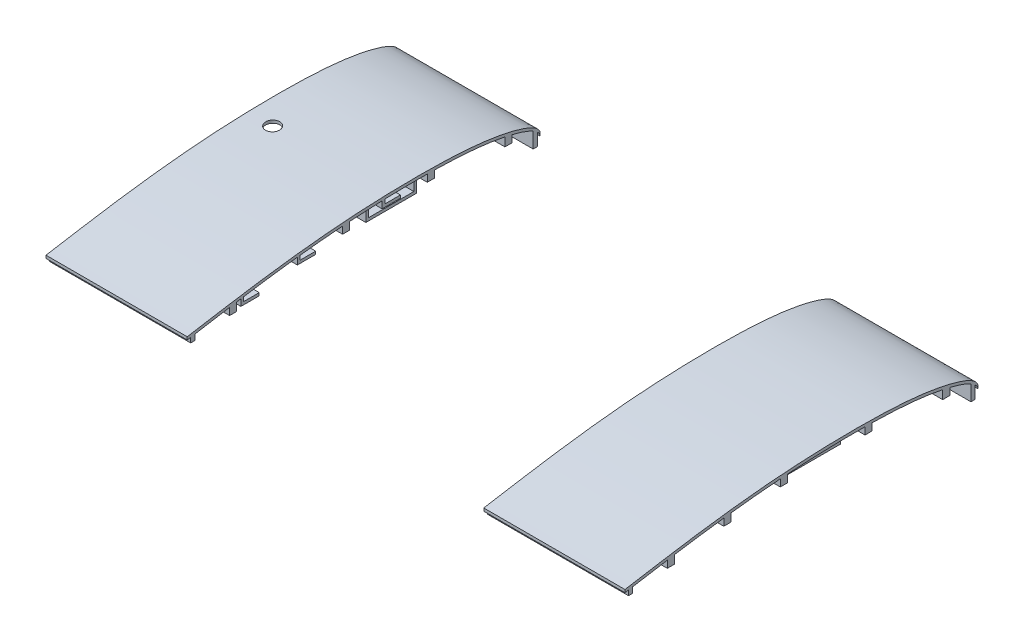
SolidWorks part; units mm, degrees
material "Nylon 12"
ref_plane "Piano frontale" through (0, 0, 0) normal (0, 0, 1) x (1, 0, 0)
ref_plane "Piano superiore" through (0, 0, 0) normal (0, 1, 0) x (1, 0, 0)
ref_plane "Piano destro" through (0, 0, 0) normal (1, 0, 0) x (0, 0, -1)
curve "CurvaProfiloAltoSinistro"
  spline degree 3 poles (-210, 41.3424, 123.285) (-210, 41.117, 125.4273) (-210, 41.4162, 123.3284) (-210, 41.7229, 121.6445) (-210, 42.4159, 117.6221) (-210, 43.2689, 112.7464) (-210, 44.3518, 106.3634) (-210, 45.4633, 98.9772) (-210, 46.9012, 90.5604) (-210, 48.3015, 81.3004) (-210, 49.8024, 71.1631) (-210, 51.2862, 60.3524) (-210, 52.7193, 48.9891) (-210, 54.0516, 37.1914) (-210, 55.2293, 25.0724) (-210, 56.2223, 12.7438) (-210, 56.9956, 0.3116) (-210, 57.5534, -12.1112) (-210, 57.8967, -24.403) (-210, 58.0348, -36.4331) (-210, 57.962, -48.0686) (-210, 57.6641, -59.1835) (-210, 57.1309, -69.6671) (-210, 56.3294, -79.427) (-210, 55.2678, -88.3926) (-210, 53.9584, -96.5028) (-210, 52.4539, -103.7012) (-210, 50.8113, -109.9251) (-210, 49.0836, -115.1191) (-210, 47.2882, -119.2301) (-210, 45.4084, -122.2711) (-210, 43.4757, -124.1874) (-210, 41.9627, -124.9688) (-210, 40.7595, -125.0213) (-210, 39.4585, -124.5051) (-210, 38.3042, -122.3747) (-210, 37.1296, -119.3023) (-210, 36.2413, -114.9281) (-210, 35.5726, -109.3738) (-210, 35.1578, -102.5878) (-210, 34.905, -94.6381) (-210, 34.7886, -85.6028) (-210, 34.8146, -75.6013) (-210, 34.9515, -64.7547) (-210, 35.2224, -53.1982) (-210, 35.6332, -41.0592) (-210, 36.2314, -28.4539) (-210, 37.0173, -15.4799) (-210, 37.9504, -2.2329) (-210, 38.9791, 11.1764) (-210, 40.022, 24.6158) (-210, 41.0098, 37.9314) (-210, 41.876, 50.9537) (-210, 42.5596, 63.4999) (-210, 43.0032, 75.3712) (-210, 43.1376, 86.3376) (-210, 42.9932, 96.1842) (-210, 42.6673, 104.6804) (-210, 42.2441, 111.8065) (-210, 41.8557, 117.1894) (-210, 41.4787, 121.5181) (-210, 41.3424, 123.285) (-210, 41.117, 125.4273) (-210, 41.4162, 123.3284) knots -0.014202 -0.006329 -0.001589 0 0.001576 0.006211 0.01368 0.023764 0.036307 0.051658 0.068045 0.086769 0.107053 0.128647 0.151303 0.174786 0.19886 0.223309 0.247929 0.272522 0.296848 0.320648 0.343669 0.365658 0.3864 0.405741 0.423561 0.439779 0.454311 0.467034 0.477831 0.486643 0.493542 0.498786 0.50271 0.50309 0.505896 0.510322 0.516831 0.525521 0.536535 0.549945 0.565696 0.583577 0.603379 0.624844 0.647727 0.671743 0.696673 0.722357 0.748609 0.77521 0.801891 0.828329 0.854175 0.879074 0.902636 0.924421 0.943939 0.960827 0.974827 0.985798 0.993671 0.998411 1 1.001576 1.006211 1.01368 periodic
curve "CurvaProfiloBassoSinistro"
  spline degree 3 poles (-210, 43.3424, 123.285) (-210, 43.117, 125.4273) (-210, 43.4162, 123.3284) (-210, 43.7229, 121.6445) (-210, 44.4159, 117.6221) (-210, 45.2689, 112.7464) (-210, 46.3518, 106.3634) (-210, 47.4633, 98.9772) (-210, 48.9012, 90.5604) (-210, 50.3015, 81.3004) (-210, 51.8024, 71.1631) (-210, 53.2862, 60.3524) (-210, 54.7193, 48.9891) (-210, 56.0516, 37.1914) (-210, 57.2293, 25.0724) (-210, 58.2223, 12.7438) (-210, 58.9956, 0.3116) (-210, 59.5534, -12.1112) (-210, 59.8967, -24.403) (-210, 60.0348, -36.4331) (-210, 59.962, -48.0686) (-210, 59.6641, -59.1835) (-210, 59.1309, -69.6671) (-210, 58.3294, -79.427) (-210, 57.2678, -88.3926) (-210, 55.9584, -96.5028) (-210, 54.4539, -103.7012) (-210, 52.8113, -109.9251) (-210, 51.0836, -115.1191) (-210, 49.2882, -119.2301) (-210, 47.4084, -122.2711) (-210, 45.4757, -124.1874) (-210, 43.9627, -124.9688) (-210, 42.7595, -125.0213) (-210, 41.4585, -124.5051) (-210, 40.3042, -122.3747) (-210, 39.1296, -119.3023) (-210, 38.2413, -114.9281) (-210, 37.5726, -109.3738) (-210, 37.1578, -102.5878) (-210, 36.905, -94.6381) (-210, 36.7886, -85.6028) (-210, 36.8146, -75.6013) (-210, 36.9515, -64.7547) (-210, 37.2224, -53.1982) (-210, 37.6332, -41.0592) (-210, 38.2314, -28.4539) (-210, 39.0173, -15.4799) (-210, 39.9504, -2.2329) (-210, 40.9791, 11.1764) (-210, 42.022, 24.6158) (-210, 43.0098, 37.9314) (-210, 43.876, 50.9537) (-210, 44.5596, 63.4999) (-210, 45.0032, 75.3712) (-210, 45.1376, 86.3376) (-210, 44.9932, 96.1842) (-210, 44.6673, 104.6804) (-210, 44.2441, 111.8065) (-210, 43.8557, 117.1894) (-210, 43.4787, 121.5181) (-210, 43.3424, 123.285) (-210, 43.117, 125.4273) (-210, 43.4162, 123.3284) knots -0.014202 -0.006329 -0.001589 0 0.001576 0.006211 0.01368 0.023764 0.036307 0.051658 0.068045 0.086769 0.107053 0.128647 0.151303 0.174786 0.19886 0.223309 0.247929 0.272522 0.296848 0.320648 0.343669 0.365658 0.3864 0.405741 0.423561 0.439779 0.454311 0.467034 0.477831 0.486643 0.493542 0.498786 0.50271 0.50309 0.505896 0.510322 0.516831 0.525521 0.536535 0.549945 0.565696 0.583577 0.603379 0.624844 0.647727 0.671743 0.696673 0.722357 0.748609 0.77521 0.801891 0.828329 0.854175 0.879074 0.902636 0.924421 0.943939 0.960827 0.974827 0.985798 0.993671 0.998411 1 1.001576 1.006211 1.01368 periodic
ref_plane "PianoProfiloSinistro" through (-210, 0, 0) normal (1, 0, 0) x (0, 0, -1)
sketch "ProfiloSinistro" plane through (-210, 0, 0) normal (1, 0, 0) x (0, 0, -1)
  line L0 (-125, 43.17) -> (-125, 41.17)
  line L1 (125.0001, 43.1872) -> (125.0001, 41.1872)
  line L2 (122.5001, 43.1872) -> (127.5001, 43.1872) construction
  line L4 (-50, 52.5724) -> (-50, 46.9555)
  line L5 (-50, 46.9555) -> (-55, 46.9555)
  line L6 (-55, 51.9555) -> (-55, 46.9555)
  line L8 (-90, 46.9622) -> (-90, 41.143)
  line L9 (-90, 41.143) -> (-95, 41.143)
  line L10 (-95, 46.143) -> (-95, 41.143)
  line L12 (-10, 56.3746) -> (-10, 51.0196)
  line L13 (-10, 51.0196) -> (-15, 51.0196)
  line L14 (-15, 56.0196) -> (-15, 51.0196)
  line L16 (50.0001, 57.8877) -> (50.0001, 52.8877)
  line L17 (50.0001, 52.8877) -> (45.0001, 52.8877)
  line L18 (45.0001, 57.965) -> (45.0001, 52.8877)
  line L20 (105.0001, 52.079) -> (105.0001, 47.079)
  line L21 (105.0001, 47.079) -> (100.0001, 47.079)
  line L22 (100.0001, 53.212) -> (100.0001, 47.079)
  line L24 (137.7468, 0) -> (-137.7468, 0) construction
  spline S0 degree 3 poles (-123.3284, 43.4162) (-125.4273, 43.117) (-123.285, 43.3424) (-121.5181, 43.4787) (-117.1894, 43.8557) (-111.8065, 44.2441) (-104.6804, 44.6673) (-96.1842, 44.9932) (-86.3376, 45.1376) (-75.3712, 45.0032) (-63.4999, 44.5596) (-50.9537, 43.876) (-37.9314, 43.0098) (-24.6158, 42.022) (-11.1764, 40.9791) (2.2329, 39.9504) (15.4799, 39.0173) (28.4539, 38.2314) (41.0592, 37.6332) (53.1982, 37.2224) (64.7547, 36.9515) (75.6013, 36.8146) (85.6028, 36.7886) (94.6381, 36.905) (102.5878, 37.1578) (109.3738, 37.5726) (114.9281, 38.2413) (119.3023, 39.1296) (122.3747, 40.3042) (124.5051, 41.4585) (125.0213, 42.7595) (124.9688, 43.9627) (124.1874, 45.4757) (122.2711, 47.4084) (119.2301, 49.2882) (115.1191, 51.0836) (109.9251, 52.8113) (103.7012, 54.4539) (96.5028, 55.9584) (88.3926, 57.2678) (79.427, 58.3294) (69.6671, 59.1309) (59.1835, 59.6641) (48.0686, 59.962) (36.4331, 60.0348) (24.403, 59.8967) (12.1112, 59.5534) (-0.3116, 58.9956) (-12.7438, 58.2223) (-25.0724, 57.2293) (-37.1914, 56.0516) (-48.9891, 54.7193) (-60.3524, 53.2862) (-71.1631, 51.8024) (-81.3004, 50.3015) (-90.5604, 48.9012) (-98.9772, 47.4633) (-106.3634, 46.3518) (-112.7464, 45.2689) (-117.6221, 44.4159) (-121.6445, 43.7229) (-123.3284, 43.4162) (-125.4273, 43.117) (-123.285, 43.3424) knots -0.01368 -0.006211 -0.001576 0 0.001589 0.006329 0.014202 0.025173 0.039173 0.056061 0.075579 0.097364 0.120926 0.145825 0.171671 0.198109 0.22479 0.251391 0.277643 0.303327 0.328257 0.352273 0.375156 0.396621 0.416423 0.434304 0.450055 0.463465 0.474479 0.483169 0.489678 0.494104 0.49691 0.49729 0.501214 0.506458 0.513357 0.522169 0.532966 0.545689 0.560221 0.576439 0.594259 0.6136 0.634342 0.656331 0.679352 0.703152 0.727478 0.752071 0.776691 0.80114 0.825214 0.848697 0.871353 0.892947 0.913231 0.931955 0.948342 0.963693 0.976236 0.98632 0.993789 0.998424 1 1.001589 1.006329 1.014202 only from (-125, 43.17) to (-125, 43.17) construction
  spline S1 degree 3 poles (125.0001, 43.1872) (125.0001, 43.2458) (124.9661, 43.968) (124.1874, 45.4757) (122.2711, 47.4084) (119.2301, 49.2882) (115.1191, 51.0836) (109.9251, 52.8113) (103.7012, 54.4539) (96.5028, 55.9584) (88.3926, 57.2678) (79.427, 58.3294) (69.6671, 59.1309) (59.1835, 59.6641) (48.0686, 59.962) (36.4331, 60.0348) (24.403, 59.8967) (12.1112, 59.5534) (-0.3116, 58.9956) (-12.7438, 58.2223) (-25.0724, 57.2293) (-37.1914, 56.0516) (-48.9891, 54.7193) (-60.3524, 53.2862) (-71.1631, 51.8024) (-81.3004, 50.3015) (-90.5604, 48.9012) (-98.9772, 47.4633) (-106.3634, 46.3518) (-112.7464, 45.2689) (-117.6221, 44.4159) (-121.6445, 43.7229) (-123.3284, 43.4162) (-124.9998, 43.178) (-125, 43.17) knots 0.496944 0.496944 0.496944 0.496944 0.49729 0.501214 0.506458 0.513357 0.522169 0.532966 0.545689 0.560221 0.576439 0.594259 0.6136 0.634342 0.656331 0.679352 0.703152 0.727478 0.752071 0.776691 0.80114 0.825214 0.848697 0.871353 0.892947 0.913231 0.931955 0.948342 0.963693 0.976236 0.98632 0.993789 0.998424 1 1 1 1
  spline S3 degree 3 poles (125.0001, 41.1872) (125.0001, 41.2458) (124.9661, 41.968) (124.1874, 43.4757) (122.2711, 45.4084) (119.2301, 47.2882) (115.1191, 49.0836) (110.2558, 50.7013) (106.751, 51.647) (105.0001, 52.079) knots 0.496944 0.496944 0.496944 0.496944 0.49729 0.501214 0.506458 0.513357 0.522169 0.532966 0.54363 0.54363 0.54363 0.54363
  spline S4 degree 3 poles (-95, 46.143) (-96.3836, 45.9134) (-100.3273, 45.2601) (-106.3634, 44.3518) (-112.7464, 43.2689) (-117.6221, 42.4159) (-121.6445, 41.7229) (-123.3284, 41.4162) (-124.9998, 41.178) (-125, 41.17) knots 0.940049 0.940049 0.940049 0.940049 0.948342 0.963693 0.976236 0.98632 0.993789 0.998424 1 1 1 1
  spline S5 degree 3 poles (-55, 51.9555) (-56.8432, 51.723) (-62.3071, 51.0179) (-71.1631, 49.8024) (-80.9841, 48.3484) (-87.1888, 47.411) (-90, 46.9622) knots 0.860366 0.860366 0.860366 0.860366 0.871353 0.892947 0.913231 0.930064 0.930064 0.930064 0.930064
  spline S6 degree 3 poles (-15, 56.0196) (-18.3794, 55.7673) (-25.8142, 55.1572) (-37.1914, 54.0516) (-45.4742, 53.1162) (-49.7084, 52.6076) (-50, 52.5724) knots 0.781099 0.781099 0.781099 0.781099 0.80114 0.825214 0.848697 0.850435 0.850435 0.850435 0.850435
  spline S7 degree 3 poles (45.0001, 57.965) (42.1885, 57.9961) (35.3522, 58.0224) (24.403, 57.8967) (12.1112, 57.5534) (0.613, 57.0371) (-6.7697, 56.5921) (-10, 56.3746) knots 0.662724 0.662724 0.662724 0.662724 0.679352 0.703152 0.727478 0.752071 0.771218 0.771218 0.771218 0.771218
  spline S8 degree 3 poles (100.0001, 53.212) (98.9265, 53.4351) (95.1591, 54.1753) (88.3926, 55.2678) (79.427, 56.3294) (69.6671, 57.1309) (59.7687, 57.6343) (53.1316, 57.8251) (50.0001, 57.8877) knots 0.553737 0.553737 0.553737 0.553737 0.560221 0.576439 0.594259 0.6136 0.634342 0.652866 0.652866 0.652866 0.652866
  point P24 (125.0001, 43.1872)
  dimension "D1" = 5
  dimension "D2" = 5
  dimension "D3" = 5.8192
  dimension "D4" = 41.17
  dimension "D5" = 46.143
  dimension "D6" = 30
  dimension "D7" = 41.143
  dimension "D8" = 5
  dimension "D9" = 43.1872
  dimension "D10" = 35
  dimension "D11" = 4.9933
  dimension "D12" = 46.9555
  dimension "D13" = 51.0196
  dimension "D14" = 35
  dimension "D15" = 56.0196
  dimension "D16" = 52.5724
  dimension "D17" = 56.3746
  dimension "D18" = 5.0773
  dimension "D19" = 5
  dimension "D20" = 55.0001
  dimension "D21" = 52.8877
  dimension "D22" = 47.079
  dimension "D23" = 50
  dimension "D24" = 6.133
  dimension "D25" = 5
  dimension "D26" = 20
  dimension "D27" = 2
extrude "ProfiloConRinforziSinistro" add sketch "ProfiloSinistro" along normal blind 105
ref_plane "PianoFrontale" through (0, 0, -125.0001) normal (0, 0, -1) x (-1, 0, 0)
sketch "Schizzo2" plane through (0, 0, -125.0001) normal (0, 0, -1) x (-1, 0, 0)
  line L0 (210, 34.6211) -> (210, -34.6211) construction
  line L1 (105, 43.1872) -> (210, 43.1872)
  line L2 (105, 43.1872) -> (105, -2.9128)
  line L3 (105, -2.9128) -> (210, -2.9128)
  line L4 (210, 43.1872) -> (210, -2.9128)
  line L6 (157.5, 43.1872) -> (157.5, -2.9128) construction
  circle A0 centre (174.165, 22.0872) radius 10
  dimension "D2" = 20
  dimension "D1" = 46.1
  dimension "D3" = 25
  dimension "D4" = 16.665
curve "CurvaProfiloAltoDestro"
  spline degree 3 poles (210, 43.3424, 123.285) (210, 43.117, 125.4273) (210, 43.4162, 123.3284) (210, 43.7229, 121.6445) (210, 44.4159, 117.6221) (210, 45.2689, 112.7464) (210, 46.3518, 106.3634) (210, 47.4633, 98.9772) (210, 48.9012, 90.5604) (210, 50.3015, 81.3004) (210, 51.8024, 71.1631) (210, 53.2862, 60.3524) (210, 54.7193, 48.9891) (210, 56.0516, 37.1914) (210, 57.2293, 25.0724) (210, 58.2223, 12.7438) (210, 58.9956, 0.3116) (210, 59.5534, -12.1112) (210, 59.8967, -24.403) (210, 60.0348, -36.4331) (210, 59.962, -48.0686) (210, 59.6641, -59.1835) (210, 59.1309, -69.6671) (210, 58.3294, -79.427) (210, 57.2678, -88.3926) (210, 55.9584, -96.5028) (210, 54.4539, -103.7012) (210, 52.8113, -109.9251) (210, 51.0836, -115.1191) (210, 49.2882, -119.2301) (210, 47.4084, -122.2711) (210, 45.4757, -124.1874) (210, 43.9627, -124.9688) (210, 42.7595, -125.0213) (210, 41.4585, -124.5051) (210, 40.3042, -122.3747) (210, 39.1296, -119.3023) (210, 38.2413, -114.9281) (210, 37.5726, -109.3738) (210, 37.1578, -102.5878) (210, 36.905, -94.6381) (210, 36.7886, -85.6028) (210, 36.8146, -75.6013) (210, 36.9515, -64.7547) (210, 37.2224, -53.1982) (210, 37.6332, -41.0592) (210, 38.2314, -28.4539) (210, 39.0173, -15.4799) (210, 39.9504, -2.2329) (210, 40.9791, 11.1764) (210, 42.022, 24.6158) (210, 43.0098, 37.9314) (210, 43.876, 50.9537) (210, 44.5596, 63.4999) (210, 45.0032, 75.3712) (210, 45.1376, 86.3376) (210, 44.9932, 96.1842) (210, 44.6673, 104.6804) (210, 44.2441, 111.8065) (210, 43.8557, 117.1894) (210, 43.4787, 121.5181) (210, 43.3424, 123.285) (210, 43.117, 125.4273) (210, 43.4162, 123.3284) knots -0.014202 -0.006329 -0.001589 0 0.001576 0.006211 0.01368 0.023764 0.036307 0.051658 0.068045 0.086769 0.107053 0.128647 0.151303 0.174786 0.19886 0.223309 0.247929 0.272522 0.296848 0.320648 0.343669 0.365658 0.3864 0.405741 0.423561 0.439779 0.454311 0.467034 0.477831 0.486643 0.493542 0.498786 0.50271 0.50309 0.505896 0.510322 0.516831 0.525521 0.536535 0.549945 0.565696 0.583577 0.603379 0.624844 0.647727 0.671743 0.696673 0.722357 0.748609 0.77521 0.801891 0.828329 0.854175 0.879074 0.902636 0.924421 0.943939 0.960827 0.974827 0.985798 0.993671 0.998411 1 1.001576 1.006211 1.01368 periodic
curve "CurvaProfiloBassoDestro"
  spline degree 3 poles (210, 41.3424, 123.285) (210, 41.117, 125.4273) (210, 41.4162, 123.3284) (210, 41.7229, 121.6445) (210, 42.4159, 117.6221) (210, 43.2689, 112.7464) (210, 44.3518, 106.3634) (210, 45.4633, 98.9772) (210, 46.9012, 90.5604) (210, 48.3015, 81.3004) (210, 49.8024, 71.1631) (210, 51.2862, 60.3524) (210, 52.7193, 48.9891) (210, 54.0516, 37.1914) (210, 55.2293, 25.0724) (210, 56.2223, 12.7438) (210, 56.9956, 0.3116) (210, 57.5534, -12.1112) (210, 57.8967, -24.403) (210, 58.0348, -36.4331) (210, 57.962, -48.0686) (210, 57.6641, -59.1835) (210, 57.1309, -69.6671) (210, 56.3294, -79.427) (210, 55.2678, -88.3926) (210, 53.9584, -96.5028) (210, 52.4539, -103.7012) (210, 50.8113, -109.9251) (210, 49.0836, -115.1191) (210, 47.2882, -119.2301) (210, 45.4084, -122.2711) (210, 43.4757, -124.1874) (210, 41.9627, -124.9688) (210, 40.7595, -125.0213) (210, 39.4585, -124.5051) (210, 38.3042, -122.3747) (210, 37.1296, -119.3023) (210, 36.2413, -114.9281) (210, 35.5726, -109.3738) (210, 35.1578, -102.5878) (210, 34.905, -94.6381) (210, 34.7886, -85.6028) (210, 34.8146, -75.6013) (210, 34.9515, -64.7547) (210, 35.2224, -53.1982) (210, 35.6332, -41.0592) (210, 36.2314, -28.4539) (210, 37.0173, -15.4799) (210, 37.9504, -2.2329) (210, 38.9791, 11.1764) (210, 40.022, 24.6158) (210, 41.0098, 37.9314) (210, 41.876, 50.9537) (210, 42.5596, 63.4999) (210, 43.0032, 75.3712) (210, 43.1376, 86.3376) (210, 42.9932, 96.1842) (210, 42.6673, 104.6804) (210, 42.2441, 111.8065) (210, 41.8557, 117.1894) (210, 41.4787, 121.5181) (210, 41.3424, 123.285) (210, 41.117, 125.4273) (210, 41.4162, 123.3284) knots -0.014202 -0.006329 -0.001589 0 0.001576 0.006211 0.01368 0.023764 0.036307 0.051658 0.068045 0.086769 0.107053 0.128647 0.151303 0.174786 0.19886 0.223309 0.247929 0.272522 0.296848 0.320648 0.343669 0.365658 0.3864 0.405741 0.423561 0.439779 0.454311 0.467034 0.477831 0.486643 0.493542 0.498786 0.50271 0.50309 0.505896 0.510322 0.516831 0.525521 0.536535 0.549945 0.565696 0.583577 0.603379 0.624844 0.647727 0.671743 0.696673 0.722357 0.748609 0.77521 0.801891 0.828329 0.854175 0.879074 0.902636 0.924421 0.943939 0.960827 0.974827 0.985798 0.993671 0.998411 1 1.001576 1.006211 1.01368 periodic
ref_plane "PianoProfiloDestro" through (210, 0, 0) normal (1, 0, 0) x (0, 0, -1)
sketch "Schizzo5" plane through (210, 0, 0) normal (1, 0, 0) x (0, 0, -1)
  line L0 (-125, 43.17) -> (-125, 41.17)
  line L1 (125.0001, 43.1872) -> (125.0001, 41.1872)
  line L2 (119.6216, 43.1872) -> (129.6216, 43.1872) construction
  line L3 (137.5117, 0) -> (-137.5117, 0) construction
  line L6 (-90, 46.9622) -> (-90, 41.143)
  line L7 (-90, 41.143) -> (-95, 41.143)
  line L8 (-95, 46.143) -> (-95, 41.143)
  line L10 (-50, 52.5724) -> (-50, 46.9555)
  line L11 (-50, 46.9555) -> (-55, 46.9555)
  line L12 (-55, 51.9555) -> (-55, 46.9555)
  line L14 (-10, 56.3746) -> (-10, 51.0196)
  line L15 (-10, 51.0196) -> (-15, 51.0196)
  line L16 (-15, 56.0196) -> (-15, 51.0196)
  line L18 (50.0001, 57.8877) -> (50.0001, 52.8877)
  line L19 (50.0001, 52.8877) -> (45.0001, 52.8877)
  line L20 (45.0001, 57.965) -> (45.0001, 52.8877)
  line L22 (105.0001, 52.079) -> (105.0001, 47.079)
  line L23 (105.0001, 47.079) -> (100.0001, 47.079)
  line L24 (100.0001, 53.212) -> (100.0001, 47.079)
  spline S0 degree 3 poles (-123.3284, 43.4162) (-125.4273, 43.117) (-123.285, 43.3424) (-121.5181, 43.4787) (-117.1894, 43.8557) (-111.8065, 44.2441) (-104.6804, 44.6673) (-96.1842, 44.9932) (-86.3376, 45.1376) (-75.3712, 45.0032) (-63.4999, 44.5596) (-50.9537, 43.876) (-37.9314, 43.0098) (-24.6158, 42.022) (-11.1764, 40.9791) (2.2329, 39.9504) (15.4799, 39.0173) (28.4539, 38.2314) (41.0592, 37.6332) (53.1982, 37.2224) (64.7547, 36.9515) (75.6013, 36.8146) (85.6028, 36.7886) (94.6381, 36.905) (102.5878, 37.1578) (109.3738, 37.5726) (114.9281, 38.2413) (119.3023, 39.1296) (122.3747, 40.3042) (124.5051, 41.4585) (125.0213, 42.7595) (124.9688, 43.9627) (124.1874, 45.4757) (122.2711, 47.4084) (119.2301, 49.2882) (115.1191, 51.0836) (109.9251, 52.8113) (103.7012, 54.4539) (96.5028, 55.9584) (88.3926, 57.2678) (79.427, 58.3294) (69.6671, 59.1309) (59.1835, 59.6641) (48.0686, 59.962) (36.4331, 60.0348) (24.403, 59.8967) (12.1112, 59.5534) (-0.3116, 58.9956) (-12.7438, 58.2223) (-25.0724, 57.2293) (-37.1914, 56.0516) (-48.9891, 54.7193) (-60.3524, 53.2862) (-71.1631, 51.8024) (-81.3004, 50.3015) (-90.5604, 48.9012) (-98.9772, 47.4633) (-106.3634, 46.3518) (-112.7464, 45.2689) (-117.6221, 44.4159) (-121.6445, 43.7229) (-123.3284, 43.4162) (-125.4273, 43.117) (-123.285, 43.3424) knots -0.01368 -0.006211 -0.001576 0 0.001589 0.006329 0.014202 0.025173 0.039173 0.056061 0.075579 0.097364 0.120926 0.145825 0.171671 0.198109 0.22479 0.251391 0.277643 0.303327 0.328257 0.352273 0.375156 0.396621 0.416423 0.434304 0.450055 0.463465 0.474479 0.483169 0.489678 0.494104 0.49691 0.49729 0.501214 0.506458 0.513357 0.522169 0.532966 0.545689 0.560221 0.576439 0.594259 0.6136 0.634342 0.656331 0.679352 0.703152 0.727478 0.752071 0.776691 0.80114 0.825214 0.848697 0.871353 0.892947 0.913231 0.931955 0.948342 0.963693 0.976236 0.98632 0.993789 0.998424 1 1.001589 1.006329 1.014202 only from (-125, 43.17) to (-125, 43.17) construction
  spline S1 degree 3 poles (125.0001, 43.1872) (125.0001, 43.2458) (124.9661, 43.968) (124.1874, 45.4757) (122.2711, 47.4084) (119.2301, 49.2882) (115.1191, 51.0836) (109.9251, 52.8113) (103.7012, 54.4539) (96.5028, 55.9584) (88.3926, 57.2678) (79.427, 58.3294) (69.6671, 59.1309) (59.1835, 59.6641) (48.0686, 59.962) (36.4331, 60.0348) (24.403, 59.8967) (12.1112, 59.5534) (-0.3116, 58.9956) (-12.7438, 58.2223) (-25.0724, 57.2293) (-37.1914, 56.0516) (-48.9891, 54.7193) (-60.3524, 53.2862) (-71.1631, 51.8024) (-81.3004, 50.3015) (-90.5604, 48.9012) (-98.9772, 47.4633) (-106.3634, 46.3518) (-112.7464, 45.2689) (-117.6221, 44.4159) (-121.6445, 43.7229) (-123.3284, 43.4162) (-124.9998, 43.178) (-125, 43.17) knots 0.496944 0.496944 0.496944 0.496944 0.49729 0.501214 0.506458 0.513357 0.522169 0.532966 0.545689 0.560221 0.576439 0.594259 0.6136 0.634342 0.656331 0.679352 0.703152 0.727478 0.752071 0.776691 0.80114 0.825214 0.848697 0.871353 0.892947 0.913231 0.931955 0.948342 0.963693 0.976236 0.98632 0.993789 0.998424 1 1 1 1
  spline S3 degree 3 poles (125.0001, 41.1872) (125.0001, 41.2458) (124.9661, 41.968) (124.1874, 43.4757) (122.2711, 45.4084) (119.2301, 47.2882) (115.1191, 49.0836) (110.2558, 50.7013) (106.751, 51.647) (105.0001, 52.079) knots 0.496944 0.496944 0.496944 0.496944 0.49729 0.501214 0.506458 0.513357 0.522169 0.532966 0.54363 0.54363 0.54363 0.54363
  spline S4 degree 3 poles (45.0001, 57.965) (42.1885, 57.9961) (35.3522, 58.0224) (24.403, 57.8967) (12.1112, 57.5534) (0.613, 57.0371) (-6.7697, 56.5921) (-10, 56.3746) knots 0.662724 0.662724 0.662724 0.662724 0.679352 0.703152 0.727478 0.752071 0.771218 0.771218 0.771218 0.771218
  spline S5 degree 3 poles (100.0001, 53.212) (98.9265, 53.4351) (95.1591, 54.1753) (88.3926, 55.2678) (79.427, 56.3294) (69.6671, 57.1309) (59.7687, 57.6343) (53.1316, 57.8251) (50.0001, 57.8877) knots 0.553737 0.553737 0.553737 0.553737 0.560221 0.576439 0.594259 0.6136 0.634342 0.652866 0.652866 0.652866 0.652866
  spline S6 degree 3 poles (-15, 56.0196) (-18.3794, 55.7673) (-25.8142, 55.1572) (-37.1914, 54.0516) (-45.4742, 53.1162) (-49.7084, 52.6076) (-50, 52.5724) knots 0.781099 0.781099 0.781099 0.781099 0.80114 0.825214 0.848697 0.850435 0.850435 0.850435 0.850435
  spline S7 degree 3 poles (-55, 51.9555) (-56.8432, 51.723) (-62.3071, 51.0179) (-71.1631, 49.8024) (-80.9841, 48.3484) (-87.1888, 47.411) (-90, 46.9622) knots 0.860366 0.860366 0.860366 0.860366 0.871353 0.892947 0.913231 0.930064 0.930064 0.930064 0.930064
  spline S8 degree 3 poles (-95, 46.143) (-96.3836, 45.9134) (-100.3273, 45.2601) (-106.3634, 44.3518) (-112.7464, 43.2689) (-117.6221, 42.4159) (-121.6445, 41.7229) (-123.3284, 41.4162) (-124.9998, 41.178) (-125, 41.17) knots 0.940049 0.940049 0.940049 0.940049 0.948342 0.963693 0.976236 0.98632 0.993789 0.998424 1 1 1 1
  dimension "D1" = 10
  dimension "D2" = 43.1872
  dimension "D3" = 5
  dimension "D4" = 5
  dimension "D5" = 30
  dimension "D6" = 35
  dimension "D7" = 35
  dimension "D8" = 20
  dimension "D9" = 50
  dimension "D10" = 2
  dimension "D11" = 41.17
  dimension "D12" = 4.973
  dimension "D13" = 4.9933
  dimension "D14" = 5.8192
  dimension "D15" = 5.6169
  dimension "D16" = 5
  dimension "D17" = 3.4472
  dimension "D18" = 55.0001
  dimension "D19" = 5.355
  dimension "D20" = 5.0379
  dimension "D21" = 5
  dimension "D22" = 5
  dimension "D23" = 5.0773
  dimension "D24" = 5
  dimension "D25" = 1.5904
  dimension "D26" = 4.6757
  dimension "D27" = 6.133
  dimension "D28" = 5
  dimension "D29" = 10.8917
  dimension "D30" = 5
extrude "ProfiloConRinforziDestro" add sketch "Schizzo5" against normal blind 105 separate body
ref_plane "PianoMedioDestro" through (157.5, 0, 0) normal (1, 0, 0) x (0, 0, -1)
ref_plane "PianoMedioSinistro" through (-157.5, 0, 0) normal (-1, 0, 0) x (0, 0, 1)
sketch "Schizzo10" plane through (157.5, 0, 0) normal (1, 0, 0) x (0, 0, -1)
  line L0 (-10, 56.5064) -> (-10, 38.5064)
  line L1 (-10, 38.5064) -> (45, 38.5064)
  line L2 (45, 38.5064) -> (45, 57.9838)
  line L3 (45, 57.9838) -> (43, 57.9838)
  line L4 (43, 57.9838) -> (43, 40.5064)
  line L5 (43, 40.5064) -> (-8, 40.5064)
  line L6 (-8, 40.5064) -> (-8, 56.5064)
  line L7 (-8, 56.5064) -> (-10, 56.5064)
  line L8 (-10, 51.0196) -> (-10, 56.3746) construction
  spline S0 degree 3 poles (-10, 56.3746) (-6.7697, 56.5921) (0.613, 57.0371) (12.1112, 57.5534) (24.403, 57.8967) (35.3522, 58.0224) (42.1885, 57.9961) (45.0001, 57.965) knots 0.662724 0.662724 0.662724 0.662724 0.68187 0.706463 0.730789 0.754589 0.771218 0.771218 0.771218 0.771218 construction
  dimension "D1" = 55
  dimension "D2" = 2
  dimension "D3" = 2
  dimension "D4" = 16
  dimension "D5" = 2
extrude "CassettoGPS" add sketch "Schizzo10" along normal blind 30 and the other way blind 28
sketch "Schizzo11" plane through (187.5, 0, 0) normal (1, 0, 0) x (0, 0, -1)
  line L0 (-15, 51.0196) -> (-10, 51.0196) construction
  line L1 (-10, 38.5064) -> (45, 38.5064)
  line L2 (-10, 38.5064) -> (-10, 51.0196)
  line L3 (-10, 51.0196) -> (45, 51.0196)
  line L4 (45, 38.5064) -> (45, 51.0196)
  line L6 (-10, 38.5064) -> (45, 38.5064) construction
extrude "ChiusuraCassettoGPS" add sketch "Schizzo11" against normal blind 2
sketch "Schizzo12" plane through (-157.5, 0, 0) normal (-1, 0, 0) x (0, 0, 1)
  line L0 (-45, 57.9838) -> (-45, 42.477)
  line L1 (-45, 42.477) -> (-9, 42.477)
  line L2 (-9, 42.477) -> (-9, 57.477)
  line L3 (-9, 57.477) -> (-11, 57.477)
  line L4 (-11, 57.477) -> (-11, 44.477)
  line L5 (-11, 44.477) -> (-43, 44.477)
  line L6 (-43, 44.477) -> (-43, 57.9838)
  line L7 (-43, 57.9838) -> (-45, 57.9838)
  line L9 (-45, 38.5064) -> (-45, 57.965) construction
  spline S0 degree 3 poles (10, 56.3746) (6.7697, 56.5921) (-0.613, 57.0371) (-12.1112, 57.5534) (-24.403, 57.8967) (-35.3522, 58.0224) (-42.1885, 57.9961) (-45.0001, 57.965) knots 0.662724 0.662724 0.662724 0.662724 0.68187 0.706463 0.730789 0.754589 0.771218 0.771218 0.771218 0.771218 construction
  dimension "D1" = 2
  dimension "D2" = 2
  dimension "D3" = 2
  dimension "D4" = 32
  dimension "D5" = 13
extrude "CassettoTelemetria" add sketch "Schizzo12" along normal blind 5 and the other way blind 45
sketch "Schizzo13" plane through (-162.5, 0, 0) normal (-1, 0, 0) x (0, 0, 1)
  line L1 (-45, 42.477) -> (-27, 42.477)
  line L2 (-45, 42.477) -> (-45, 52.8877)
  line L3 (-45, 52.8877) -> (-27, 52.8877)
  line L4 (-27, 42.477) -> (-27, 52.8877)
  line L5 (-45.0001, 52.8877) -> (-50.0001, 52.8877) construction
  line L6 (-45, 42.477) -> (-9, 42.477) construction
extrude "ChiusuraCassettoTelemetria" add sketch "Schizzo13" against normal blind 2
sketch "Schizzo14" plane through (0, 42.477, 0) normal (0, -1, 0) x (1, 0, 0)
  line L0 (-162.5, -27) -> (-112.5, -27) construction
  line L2 (-112.5, -45) -> (-112.5, -9) construction
  line L3 (-162.5, -18) -> (-187.5, -18) construction
  line L4 (-162.5, -9) -> (-162.5, -18) construction
  line L5 (-162.5, -18) -> (-162.5, -27) construction
  circle A0 centre (-187.5, -18) radius 5
  dimension "D1" = 10
  dimension "D2" = 75
extrude "ForoAntenna" cut sketch "Schizzo14" against normal through all
ref_plane "PianoInternoSinistra" through (-105, 0, 0) normal (-1, 0, 0) x (0, 0, 1)
sketch "Schizzo15" plane through (-105, 0, 0) normal (-1, 0, 0) x (0, 0, 1)
  line L0 (87, 47.7392) -> (87, 42.7392)
  line L1 (87, 42.7392) -> (74, 42.7392)
  line L2 (74, 42.7392) -> (74, 44.7392)
  line L3 (74, 44.7392) -> (85, 44.7392)
  line L4 (85, 44.7392) -> (85, 47.7392)
  line L5 (85, 47.7392) -> (87, 47.7392)
  line L12 (-13.0001, 57.6179) -> (-13.0001, 52.6179)
  line L13 (-13.0001, 52.6179) -> (-26.0001, 52.6179)
  line L14 (-26.0001, 52.6179) -> (-26.0001, 54.6179)
  line L15 (-26.0001, 54.6179) -> (-15.0001, 54.6179)
  line L16 (-15.0001, 54.6179) -> (-15.0001, 57.6179)
  line L17 (-15.0001, 57.6179) -> (-13.0001, 57.6179)
  line L24 (47, 53.1612) -> (47, 48.1612)
  line L25 (47, 48.1612) -> (34, 48.1612)
  line L26 (34, 48.1612) -> (34, 50.1612)
  line L27 (34, 50.1612) -> (45, 50.1612)
  line L28 (45, 50.1612) -> (45, 53.1612)
  line L29 (45, 53.1612) -> (47, 53.1612)
  line L37 (125, 43.17) -> (125, 41.17) construction
  line L38 (-125.0001, 41.1872) -> (-125.0001, 43.1872) construction
  spline S1 degree 3 poles (90, 46.9622) (87.1888, 47.411) (80.9841, 48.3484) (71.1631, 49.8024) (62.3071, 51.0179) (56.8432, 51.723) (55, 51.9555) knots 0.860366 0.860366 0.860366 0.860366 0.877199 0.897483 0.919077 0.930064 0.930064 0.930064 0.930064 construction
  spline S2 degree 3 poles (50, 52.5724) (49.7084, 52.6076) (45.4742, 53.1162) (37.1914, 54.0516) (25.8142, 55.1572) (18.3794, 55.7673) (15, 56.0196) knots 0.781099 0.781099 0.781099 0.781099 0.782836 0.806319 0.830393 0.850435 0.850435 0.850435 0.850435 construction
  spline S4 degree 3 poles (10, 56.3746) (6.7697, 56.5921) (-0.613, 57.0371) (-12.1112, 57.5534) (-24.403, 57.8967) (-35.3522, 58.0224) (-42.1885, 57.9961) (-45.0001, 57.965) knots 0.662724 0.662724 0.662724 0.662724 0.68187 0.706463 0.730789 0.754589 0.771218 0.771218 0.771218 0.771218 construction
  dimension "D1" = 2
  dimension "D2" = 2
  dimension "D3" = 3
  dimension "D4" = 11
  dimension "D5" = 40
  dimension "D6" = 80
  dimension "D9" = 99
extrude "IncastriDentelliSinistra" add sketch "Schizzo15" along normal blind 16
ref_plane "PianoInternoDestra" through (105, 0, 0) normal (-1, 0, 0) x (0, 0, 1)
sketch "Schizzo16" plane through (105, 0, 0) normal (-1, 0, 0) x (0, 0, 1)
  line L6 (-26.0001, 54.6179) -> (-15.0001, 54.6179)
  line L7 (-15.0001, 54.6179) -> (-15.0001, 57.6179)
  line L8 (-15.0001, 57.6179) -> (-13.0001, 57.6179)
  line L9 (-13.0001, 57.6179) -> (-13.0001, 52.6179)
  line L10 (-13.0001, 52.6179) -> (-26.0001, 52.6179)
  line L11 (-26.0001, 52.6179) -> (-26.0001, 54.6179)
  line L12 (45, 53.1612) -> (47, 53.1612)
  line L13 (47, 53.1612) -> (47, 48.1612)
  line L14 (47, 48.1612) -> (34, 48.1612)
  line L15 (34, 48.1612) -> (34, 50.1612)
  line L16 (34, 50.1612) -> (45, 50.1612)
  line L17 (45, 50.1612) -> (45, 53.1612)
  line L18 (74, 44.7392) -> (74, 42.7392)
  line L19 (74, 42.7392) -> (87, 42.7392)
  line L20 (87, 42.7392) -> (87, 47.7392)
  line L21 (87, 47.7392) -> (85, 47.7392)
  line L22 (85, 47.7392) -> (85, 44.7392)
  line L23 (85, 44.7392) -> (74, 44.7392)
extrude "IncastriDentelliDestra" add sketch "Schizzo16" against normal blind 16
sketch "Schizzo18" plane through (-210, 0, 0) normal (-1, 0, 0) x (0, 0, 1)
  line L0 (119.5, 42.0925) -> (119.5, 38.0925)
  line L1 (119.5, 38.0925) -> (122.5, 38.0925)
  line L2 (122.5, 38.0925) -> (122.5, 42.0925)
  line L3 (122.5, 42.0925) -> (119.5, 42.0925)
  line L4 (125, 43.17) -> (125, 41.17) construction
  line L5 (-125.0001, 11.8855) -> (-125.0001, -11.8855) construction
  line L6 (-123.0001, 45.7625) -> (-120.0001, 46.7625)
  line L7 (-123.0001, 45.7625) -> (-123.0001, 35.7625)
  line L8 (-123.0001, 35.7625) -> (-120.0001, 35.7625)
  line L9 (-120.0001, 46.7625) -> (-120.0001, 35.7625)
  spline S0 degree 3 poles (125, 41.17) (124.9998, 41.178) (123.3284, 41.4162) (121.6445, 41.7229) (117.6221, 42.4159) (112.7464, 43.2689) (106.3634, 44.3518) (100.3273, 45.2601) (96.3836, 45.9134) (95, 46.143) knots 0.940049 0.940049 0.940049 0.940049 0.941625 0.946261 0.953729 0.963813 0.976356 0.991707 1 1 1 1 construction
  spline S1 degree 3 poles (-105.0001, 52.079) (-106.751, 51.647) (-110.2558, 50.7013) (-115.1191, 49.0836) (-119.2301, 47.2882) (-122.2711, 45.4084) (-124.1874, 43.4757) (-124.9661, 41.968) (-125.0001, 41.2458) (-125.0001, 41.1872) knots 0.496944 0.496944 0.496944 0.496944 0.507608 0.518406 0.527217 0.534116 0.53936 0.543285 0.54363 0.54363 0.54363 0.54363 construction
  dimension "D1" = 3
  dimension "D2" = 4
  dimension "D3" = 2.5
  dimension "D4" = 3
  dimension "D5" = 11
  dimension "D6" = 2
  dimension "D7" = 1
extrude "IncastriVerticaliSinistra" add sketch "Schizzo18" against normal up to surface (105 mm away) up to face at (-105, 49.5512, 15.4881)
sketch "Schizzo19" plane through (210, 0, 0) normal (1, 0, 0) x (0, 0, -1)
  line L0 (-122.5, 41.5671) -> (-122.5, 38.0925) construction
  line L1 (-119.5, 38.0925) -> (-122.5, 38.0925)
  line L2 (-119.5, 38.0925) -> (-119.5, 42.0925)
  line L3 (-119.5, 42.0925) -> (-122.5, 42.0925)
  line L4 (-122.5, 38.0925) -> (-122.5, 42.0925)
  line L5 (120.0001, 46.7625) -> (120.0001, 35.7625)
  line L6 (120.0001, 35.7625) -> (123.0001, 35.7625) construction
  line L7 (120.0001, 35.7625) -> (123.0001, 35.7625)
  line L8 (123.0001, 35.7625) -> (123.0001, 45.7625)
  line L9 (123.0001, 45.7625) -> (120.0001, 46.7625)
  line L10 (120.0001, 46.7625) -> (120.0001, 35.7625) construction
  spline S0 degree 3 poles (-125, 41.17) (-124.9998, 41.178) (-123.3284, 41.4162) (-121.6445, 41.7229) (-117.6221, 42.4159) (-112.7464, 43.2689) (-106.3634, 44.3518) (-100.3273, 45.2601) (-96.3836, 45.9134) (-95, 46.143) knots 0.940049 0.940049 0.940049 0.940049 0.941625 0.946261 0.953729 0.963813 0.976356 0.991707 1 1 1 1 construction
  dimension "D1" = 1
extrude "IncastriVerticaliDestra" add sketch "Schizzo19" against normal up to surface (105 mm away) up to face at (105, 49.5512, 15.4881)
sketch "Schizzo20" plane through (0, 0, -125.0001) normal (0, 0, -1) x (-1, 0, 0)
  line L0 (210, 13.3946) -> (210, -13.3946) construction
  line L1 (-210, 100) -> (-205, 100)
  line L2 (-210, 100) -> (-210, 0)
  line L3 (-210, 0) -> (-205, 0)
  line L4 (-205, 100) -> (-205, 0)
  line L5 (205, 100) -> (210, 100)
  line L6 (205, 100) -> (205, 0)
  line L7 (205, 0) -> (210, 0)
  line L8 (210, 100) -> (210, 0)
  line L9 (-210, 13.3946) -> (-210, -13.3946) construction
  line L10 (137.5117, 0) -> (-137.5117, 0) construction
  dimension "D1" = 5
  dimension "D2" = 100
extrude "Taglio-Estrusione1" cut sketch "Schizzo20" against normal blind 310
sketch "Schizzo21" plane through (-105, 0, 0) normal (1, 0, 0) x (0, 0, -1)
  line L0 (-55, 46.9555) -> (-50, 46.9555)
  line L1 (-50, 46.9555) -> (-50, 52.5724)
  line L2 (-50, 52.5724) -> (-55, 51.9555)
  line L3 (-55, 51.9555) -> (-55, 46.9555)
extrude "Taglio-Estrusione2" cut sketch "Schizzo21" against normal blind 37.5
sketch "Schizzo22" plane through (105, 0, 0) normal (-1, 0, 0) x (0, 0, 1)
  line L0 (50, 46.9555) -> (55, 46.9555)
  line L1 (55, 46.9555) -> (55, 51.9555)
  line L2 (55, 51.9555) -> (55, 46.9555) construction
  line L3 (55, 51.9555) -> (50, 52.5724)
  line L4 (50, 52.5724) -> (50, 46.9555)
  spline S0 degree 3 poles (90, 46.9622) (87.1888, 47.411) (80.9841, 48.3484) (71.1631, 49.8024) (62.3071, 51.0179) (56.8432, 51.723) (55, 51.9555) knots 0.860366 0.860366 0.860366 0.860366 0.877199 0.897483 0.919077 0.930064 0.930064 0.930064 0.930064 construction
extrude "Taglio-Estrusione3" cut sketch "Schizzo22" against normal blind 37.5
